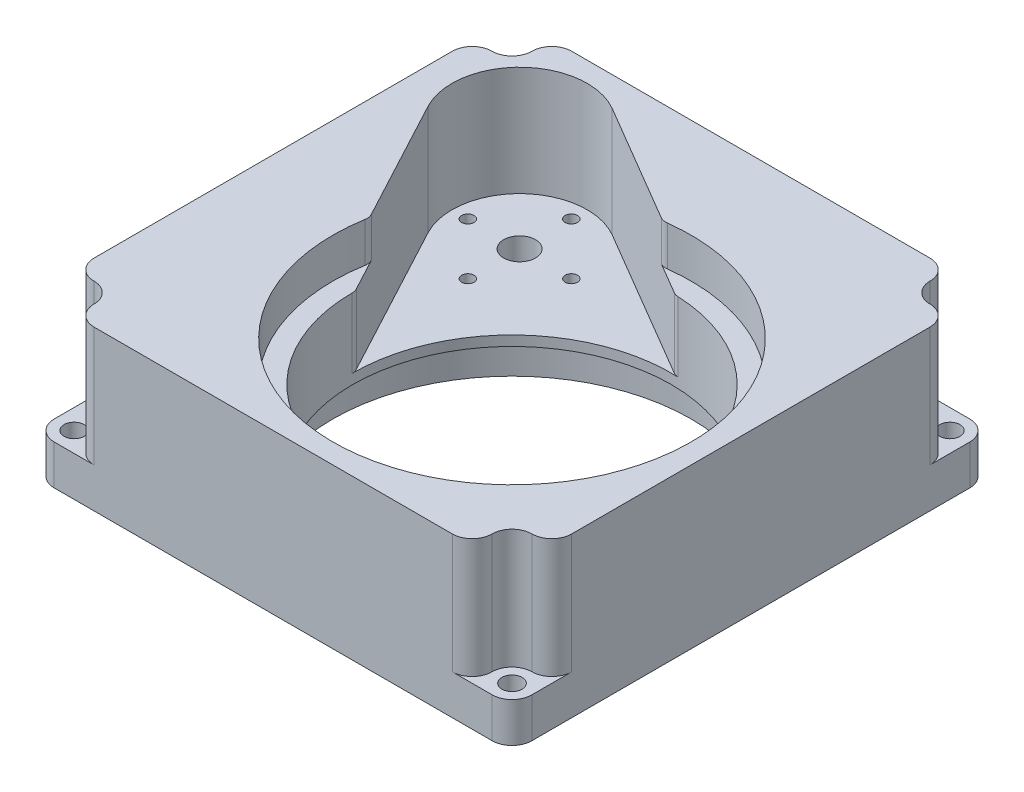
SolidWorks part; units mm, degrees
ref_plane "Front Plane" through (0, 0, 0) normal (0, 0, 1) x (1, 0, 0)
ref_plane "Top Plane" through (0, 0, 0) normal (0, 1, 0) x (1, 0, 0)
ref_plane "Right Plane" through (0, 0, 0) normal (1, 0, 0) x (0, 0, -1)
sketch "Sketch1" plane through (0, 0, 0) normal (0, 1, 0) x (1, 0, 0)
  line L1 (-60, -60) -> (60, -60)
  line L2 (-60, -60) -> (-60, 60)
  line L3 (-60, 60) -> (60, 60)
  line L4 (60, -60) -> (60, 60)
  line L5 (-60, -60) -> (60, 60) construction
  line L6 (-60, 60) -> (60, -60) construction
  point P0 (0, 0)
  dimension "D1" = 120
  dimension "D2" = 120
extrude "Boss-Extrude1" add sketch "Sketch1" along normal blind 40
sketch "Sketch2" plane through (0, 40, 0) normal (0, 1, 0) x (1, 0, 0)
  line L0 (60, -60) -> (60, 60) construction
  line L1 (-60, -60) -> (60, -60) construction
  circle A0 centre (10, -10) radius 40
  dimension "D1" = 80
  dimension "D2" = 50
  dimension "D3" = 50
extrude "Cut-Extrude1" cut sketch "Sketch2" against normal through all
sketch "Sketch3" plane through (0, 40, 0) normal (0, 1, 0) x (1, 0, 0)
  circle A0 centre (10, -10) radius 45
  dimension "D1" = 90
extrude "Cut-Extrude2" cut sketch "Sketch3" against normal blind 10
sketch "Sketch4" plane through (0, 0, 0) normal (0, -1, 0) x (1, 0, 0)
  circle A0 centre (10, 10) radius 45
  circle A1 centre (10, 10) radius 40 construction
  dimension "D1" = 90
extrude "Cut-Extrude3" cut sketch "Sketch4" against normal blind 10
sketch "Sketch11" plane through (0, 40, 0) normal (0, 1, 0) x (1, 0, 0)
  line L1 (-60, 60) -> (-50, 60)
  line L2 (-60, 60) -> (-60, 50)
  line L3 (-60, 50) -> (-50, 50)
  line L4 (-50, 60) -> (-50, 50)
  line L5 (60, 60) -> (50, 60)
  line L6 (60, 60) -> (60, 50)
  line L7 (60, 50) -> (50, 50)
  line L8 (50, 60) -> (50, 50)
  line L9 (60, -60) -> (50, -60)
  line L10 (60, -60) -> (60, -50)
  line L11 (60, -50) -> (50, -50)
  line L12 (50, -60) -> (50, -50)
  line L13 (-60, -60) -> (-50, -60)
  line L14 (-60, -60) -> (-60, -50)
  line L15 (-60, -50) -> (-50, -50)
  line L16 (-50, -60) -> (-50, -50)
  dimension "D1" = 10
  dimension "D2" = 10
  dimension "D3" = 10
  dimension "D4" = 10
  dimension "D5" = 10
  dimension "D6" = 10
  dimension "D7" = 10
extrude "Cut-Extrude8" cut sketch "Sketch11" against normal offset from surface (30 mm away) 10 up to face at (10, 0, -35)
sketch "Sketch7" plane through (0, 40, 0) normal (0, 1, 0) x (1, 0, 0)
  line L0 (-678.6068, 707.1068) -> (33947.6224, -35352.2298) construction
  circle A1 centre (-36.0598, 37.9661) radius 17
  circle A2 centre (10, -10) radius 40 construction
  dimension "D1" = 34
  dimension "D2" = 66.5
extrude "Cut-Extrude5" cut sketch "Sketch7" against normal offset from surface (27.5 mm away) 2.5 up to face at (10, 10, -35)
sketch "Sketch13" plane through (0, 0, 0) normal (0, -1, 0) x (1, 0, 0)
  circle A0 centre (-36.0598, -37.9661) radius 17
  dimension "D1" = 34
extrude "Cut-Extrude10" cut sketch "Sketch13" against normal blind 5
sketch "Sketch14" plane through (0, 12.5, 0) normal (0, 1, 0) x (1, 0, 0)
  circle A0 centre (-36.0598, 37.9661) radius 4
  circle A1 centre (-36.0598, 37.9661) radius 13 construction
  circle A2 centre (-36.0598, 50.9661) radius 1.55
  circle A3 centre (-23.0598, 37.9661) radius 1.55
  circle A4 centre (-36.0598, 24.9661) radius 1.55
  circle A5 centre (-49.0598, 37.9661) radius 1.55
  dimension "D1" = 8
  dimension "D2" = 26
  dimension "D3" = 3.1
  dimension "D4" = 3.1
  dimension "D5" = 3.1
  dimension "D6" = 3.1
extrude "Cut-Extrude11" cut sketch "Sketch14" against normal through all
sketch "Sketch10" plane through (0, 40, 0) normal (0, 1, 0) x (1, 0, 0)
  line L0 (-27.4426, 52.6203) -> (27.7412, 20.1704)
  line L1 (-51.0512, 29.95) -> (-20.8647, -26.5037)
  arc A0 (-20.8647, -26.5037) -> (27.7412, 20.1704) centre (10, -10) ccw
  arc A1 (-27.4426, 52.6203) -> (-51.0512, 29.95) centre (-36.0598, 37.9661) ccw
  circle A5 centre (-36.0598, 37.9661) radius 17 construction
  dimension "D1" = 70
  dimension "D3" = 34
extrude "Cut-Extrude7" cut sketch "Sketch10" against normal up to surface (27.5 mm away) up to face at (-49.0598, 12.5, -36.4161)
sketch "Sketch12" plane through (0, 10, 0) normal (0, 1, 0) x (1, 0, 0)
  line L0 (-60, 60) -> (-50, 50) construction
  line L1 (60, 60) -> (50, 50) construction
  line L2 (-50, -50) -> (-60, -60) construction
  line L4 (50, -50) -> (60, -60) construction
  circle A0 centre (-55, 55) radius 2.55
  circle A1 centre (55, 55) radius 2.55
  circle A2 centre (55, -55) radius 2.55
  circle A3 centre (-55, -55) radius 2.55
  dimension "D1" = 5.1
  dimension "D2" = 5.1
  dimension "D3" = 5.1
  dimension "D4" = 5.1
extrude "Cut-Extrude9" cut sketch "Sketch12" against normal through all
fillet "Fillet1" radius 5 8 edges at (50, 25, -50) (50, 25, 50) (-50, 25, 50) (-50, 25, -50) (60, 5, -60) (-60, 5, -60) (60, 5, 60) (-60, 5, 60)
fillet "Fillet2" radius 5 8 edges at (50, 25, -60) (60, 25, -50) (60, 25, 50) (-50, 25, 60) (-60, 25, 50) (-50, 25, -60) (-60, 25, -50) (50, 25, 60)
fillet "Fillet3" radius 3 4 edges at (-34.2017, 35, 1.5613) (-29.9959, 21.25, 9.4268) (11.0484, 21.25, -29.9863) (3.3598, 35, -34.5074)
